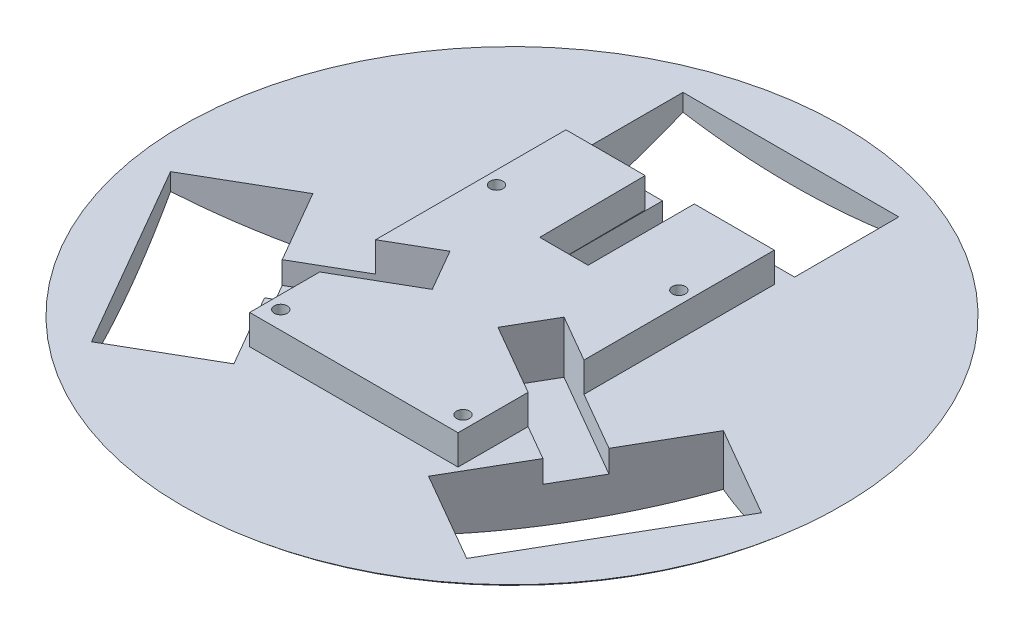
SolidWorks part; units mm, degrees
ref_plane "Front Plane" through (0, 0, 0) normal (0, 0, 1) x (1, 0, 0)
ref_plane "Top Plane" through (0, 0, 0) normal (0, 1, 0) x (1, 0, 0)
ref_plane "Right Plane" through (0, 0, 0) normal (1, 0, 0) x (0, 0, -1)
sketch "Sketch2" plane through (0, 0, 0) normal (0, 1, 0) x (1, 0, 0)
  line L0 (0, -68.0098) -> (0, 65.7503) construction
  line L1 (-29, 74.9495) -> (29, 74.9495)
  line L2 (-29, 74.9495) -> (-29, 46.9495)
  line L3 (-29, 46.9495) -> (29, 46.9495)
  line L4 (29, 74.9495) -> (29, 46.9495)
  line L5 (-29, 74.9495) -> (29, 46.9495) construction
  line L6 (-29, 46.9495) -> (29, 74.9495) construction
  line L7 (-70.2148, 0) -> (95.7201, 0) construction
  line L8 (0, 0) -> (-72.5813, -41.9048) construction
  line L9 (0, 0) -> (72.5813, -41.9048) construction
  line L10 (79.4081, -12.36) -> (50.4081, -62.5895)
  line L11 (55.1594, 1.64) -> (26.1594, -48.5895)
  line L12 (79.4081, -12.36) -> (55.1594, 1.64)
  line L13 (50.4081, -62.5895) -> (26.1594, -48.5895)
  line L14 (-50.4081, -62.5895) -> (-79.4081, -12.36)
  line L15 (-26.1594, -48.5895) -> (-55.1594, 1.64)
  line L16 (-50.4081, -62.5895) -> (-26.1594, -48.5895)
  line L17 (-79.4081, -12.36) -> (-55.1594, 1.64)
  line L18 (-6.5, -8.0505) -> (6.5, 46.9495) construction
  line L19 (-6.5, 46.9495) -> (6.5, 46.9495)
  line L20 (-6.5, 46.9495) -> (-6.5, -8.0505)
  line L21 (-6.5, -8.0505) -> (6.5, -8.0505)
  line L22 (6.5, 46.9495) -> (6.5, -8.0505)
  line L23 (-6.5, 46.9495) -> (6.5, -8.0505) construction
  line L24 (31.4023, -15.1408) -> (6.5, -0.7634)
  line L25 (-6.1216, -8.0505) -> (0, 2.5524)
  line L26 (24.9023, -26.3991) -> (0, -12.0218)
  line L27 (-25.0514, -26.4852) -> (0, -12.0218)
  line L28 (0, 2.5524) -> (6.1216, -8.0505)
  line L29 (-33.4324, -16.3129) -> (-6.5, -0.7634)
  circle A2 centre (0, 0) radius 16 construction
  point P3 (0, 19.4495)
  point P4 (0, 46.9495)
  point P6 (0, 60.9495)
  point P13 (0, 0)
  point P33 (0, 0)
  point P41 (0, -4.5162)
  dimension "D1" = 55
  dimension "D2" = 13
  dimension "D3" = 32
  dimension "D5" = 58
  dimension "D6" = 120
  dimension "D7" = 28
  dimension "D8" = 3
  dimension "D4" = 3
sketch "Sketch3" plane through (0, 0, 0) normal (1, 0, 0) x (0, 0, -1)
  line L0 (0, 83.7838) -> (0, -101.0811) construction
  line L1 (-115.9459, 0) -> (127.2973, 0) construction
  line L5 (0, 20) -> (0, 0)
  line L6 (88.569, 20) -> (0, 20)
  arc A3 (84.754, 17.3868) -> (0, 0) centre (7.3808, 179.2865) cw
  arc A4 (84.754, 17.3868) -> (88.569, 20) centre (78.286, 30.9207) ccw
  point P13 (90, 5.0684)
  dimension "D5" = 179.4384
  dimension "D1" = 15
  dimension "D2" = 20
  dimension "D3" = 20
  dimension "D4" = 90
revolve "Revolve1" add sketch "Sketch3" angle 360 about L5
extrude "Cut-Extrude1" cut sketch "Sketch2" along normal blind 40 contours L3 L4 L1 L2 | L15 L17 L14 L16 | L11 L13 L10 L12
sketch "Sketch4" plane through (0, 20, 0) normal (0, 1, 0) x (1, 0, 0)
  line L1 (-6.5, 46.9495) -> (6.5, 46.9495)
  line L2 (-6.5, 46.9495) -> (-6.5, 13.9495)
  line L3 (-6.5, 13.9495) -> (6.5, 13.9495)
  line L4 (6.5, 46.9495) -> (6.5, 13.9495)
  line L5 (-6.5, 46.9495) -> (6.5, 13.9495) construction
  line L6 (-6.5, 13.9495) -> (6.5, 46.9495) construction
  line L7 (43.9094, -17.8456) -> (37.4094, -29.1039)
  line L8 (-55.1594, 1.64) -> (-26.1594, -48.5895) construction
  line L9 (-29, 46.9495) -> (29, 46.9495) construction
  line L10 (55.1594, 1.64) -> (26.1594, -48.5895) construction
  line L26 (43.9094, -17.8456) -> (15.3306, -1.3456)
  line L27 (37.4094, -29.1039) -> (8.8306, -12.6039)
  line L28 (15.3306, -1.3456) -> (8.8306, -12.6039)
  line L29 (-37.4094, -29.1039) -> (-43.9094, -17.8456)
  line L30 (-37.4094, -29.1039) -> (-8.8306, -12.6039)
  line L31 (-43.9094, -17.8456) -> (-15.3306, -1.3456)
  line L32 (-8.8306, -12.6039) -> (-15.3306, -1.3456)
  line L33 (50.4081, -62.5895) -> (44.0538, -58.9208)
  line L34 (50.4081, -62.5895) -> (26.1594, -48.5895) construction
  line L35 (50.4081, -62.5895) -> (79.4081, -12.36)
  line L36 (79.4081, -12.36) -> (73.0538, -8.6913)
  line L37 (79.4081, -12.36) -> (55.1594, 1.64) construction
  circle A0 centre (0, 0) radius 88.569 construction
  circle A1 centre (0, 0) radius 73.569 construction
  arc A2 (44.0538, -58.9208) -> (73.0538, -8.6913) centre (0, 0) ccw
  circle A3 centre (0, 0) radius 80.3643
  point P0 (0, 30.4495)
  point P5 (0, 46.9495)
  point P22 (0, 0)
  point P23 (0, 4.0327)
  point P32 (-2.3282, 4.0326)
  line M8 (-55.1594, 1.64) -> (-26.1594, -48.5895)
  line M13 (26.1594, -48.5895) -> (55.1594, 1.64)
  line M17 (29, 46.9495) -> (-29, 46.9495)
  dimension "D4" = 177.1379
  dimension "D5" = 147.1379
  dimension "D6" = 160.7286
  dimension "D1" = 13
  dimension "D2" = 33
  dimension "D3" = 15
extrude "Cut-Extrude2" cut sketch "Sketch4" against normal blind 6 contours L4 L2 L3 M17 | L30 L32 L31 M8 | L26 L28 L27 M13 region at (0, 20, -30.4495) region at (26.37, 20, 15.2247) region at (-26.37, 20, 15.2247)
sketch "Sketch5" plane through (0, 20, 0) normal (0, 1, 0) x (1, 0, 0)
  line L0 (-28, -23.6714) -> (-8.8306, -12.6039)
  line L1 (-28, 42.5) -> (-6.7113, 42.5)
  line L2 (-28, 42.5) -> (-28, -8.6603)
  line L3 (-28, -42.5) -> (28, -42.5)
  line L4 (28, 42.5) -> (28, -8.6603)
  line L5 (-28, 42.5) -> (28, -42.5) construction
  line L6 (-28, -42.5) -> (28, 42.5) construction
  line L7 (-37.4094, -29.1039) -> (-8.8306, -12.6039) construction
  line L8 (-8.8306, -12.6039) -> (-15.3306, -1.3456)
  line L9 (-15.3306, -1.3456) -> (-28, -8.6603)
  line L10 (-43.9094, -17.8456) -> (-15.3306, -1.3456) construction
  line L11 (28, -23.6714) -> (8.8306, -12.6039)
  line L12 (37.4094, -29.1039) -> (8.8306, -12.6039) construction
  line L13 (8.8306, -12.6039) -> (15.3306, -1.3456)
  line L14 (15.3306, -1.3456) -> (28, -8.6603)
  line L15 (-6.7113, 42.5) -> (-6.5, 13.9495)
  line L16 (-6.5, 13.9495) -> (6.5, 13.9495)
  line L17 (6.5, 13.9495) -> (6.5, 42.5)
  line L18 (6.5, 46.9495) -> (6.5, 13.9495) construction
  line L19 (6.5, 46.9495) -> (6.5, 13.9495) construction
  line L20 (-28, -23.6714) -> (-28, -42.5)
  line L21 (28, -23.6714) -> (28, -42.5)
  line L22 (6.5, 42.5) -> (28, 42.5)
  line L23 (0, 13.9495) -> (0, -42.8187) construction
  line L24 (-28, -8.6603) -> (28, -8.6603) construction
  circle A0 centre (-24.5, -37.6603) radius 1.75
  circle A1 centre (24.5, -37.6603) radius 1.75
  circle A2 centre (24.5, 20.3397) radius 1.75
  circle A3 centre (-24.5, 20.3397) radius 1.75
  point P0 (0, 0)
  dimension "D3" = 3.5
  dimension "D1" = 56
  dimension "D2" = 85
  dimension "D4" = 49
  dimension "D5" = 58
extrude "Boss-Extrude1" add sketch "Sketch5" along normal blind 8
